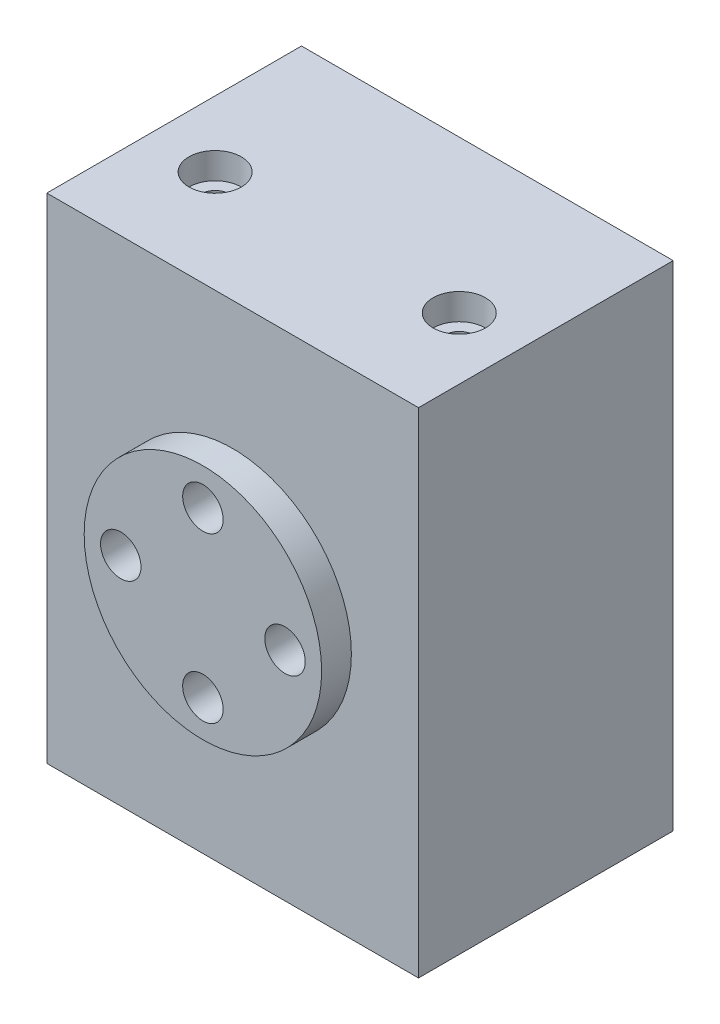
SolidWorks part; units mm, degrees
ref_plane "Front Plane" through (0, 0, 0) normal (0, 0, 1) x (1, 0, 0)
ref_plane "Top Plane" through (0, 0, 0) normal (0, 1, 0) x (1, 0, 0)
ref_plane "Right Plane" through (0, 0, 0) normal (1, 0, 0) x (0, 0, -1)
sketch "Sketch1" plane through (0, 0, 0) normal (0, 0, 1) x (1, 0, 0)
  circle A0 centre (0, 0) radius 9.975
  dimension "D1" = 19.95
extrude "Boss-Extrude1" add sketch "Sketch1" along normal blind 2.5
sketch "Sketch3" plane through (0, 0, 0) normal (0, 0, -1) x (-1, 0, 0)
  line L0 (15.615, 20.75) -> (15.615, -20.75)
  line L1 (-12.615, 17.75) -> (12.615, 17.75)
  line L2 (-12.615, 17.75) -> (-12.615, -17.75)
  line L3 (-12.615, -17.75) -> (12.615, -17.75)
  line L4 (12.615, 17.75) -> (12.615, -17.75)
  line L5 (-12.615, 17.75) -> (12.615, -17.75) construction
  line L6 (-12.615, -17.75) -> (12.615, 17.75) construction
  line L7 (-15.615, -20.75) -> (15.615, -20.75)
  line L8 (-15.615, 20.75) -> (-15.615, -20.75)
  line L9 (-15.615, 20.75) -> (15.615, 20.75)
  point P0 (0, 0)
  dimension "D1" = 35.5
  dimension "D2" = 25.23
  dimension "D3" = 3
extrude "Boss-Extrude4" add sketch "Sketch3" along normal blind 2.5 contours L2 L1 L4 L3
extrude "Boss-Extrude5" add sketch "Sketch3<5>" along normal blind 21.4
sketch "Sketch3<5>" plane through (0, 0, 0) normal (0, 0, -1) x (-1, 0, 0) same geometry as "Sketch3"
sketch "Sketch4" plane through (0, 0, -2.5) normal (0, 0, -1) x (-1, 0, 0)
  line L1 (12.615, 17.75) -> (7.415, 17.75)
  line L2 (12.615, 17.75) -> (12.615, 16.65)
  line L3 (12.615, 16.65) -> (7.415, 16.65)
  line L4 (7.415, 17.75) -> (7.415, 16.65)
  line L5 (-12.615, 17.75) -> (-7.415, 17.75)
  line L6 (-12.615, 17.75) -> (-12.615, 16.65)
  line L7 (-12.615, 16.65) -> (-7.415, 16.65)
  line L8 (-7.415, 17.75) -> (-7.415, 16.65)
  line L9 (12.615, -17.75) -> (9.415, -17.75)
  line L10 (12.615, -17.75) -> (12.615, -16.05)
  line L11 (12.615, -16.05) -> (9.415, -16.05)
  line L12 (9.415, -17.75) -> (9.415, -16.05)
  line L13 (-12.615, -17.75) -> (-9.415, -17.75)
  line L14 (-12.615, -17.75) -> (-12.615, -16.05)
  line L15 (-12.615, -16.05) -> (-9.415, -16.05)
  line L16 (-9.415, -17.75) -> (-9.415, -16.05)
  dimension "D1" = 1.1
  dimension "D2" = 5.2
  dimension "D3" = 5.2
  dimension "D4" = 1.1
  dimension "D5" = 3.2
  dimension "D6" = 1.7
  dimension "D7" = 3.2
  dimension "D8" = 1.7
extrude "Boss-Extrude6" add sketch "Sketch4" along normal blind 18.9 contours L2 L1 L4 L3 | L6 L5 L8 L7 | L10 L9 L12 L11 | L14 L13 L16 L15
sketch "Sketch6" plane through (0, 0, -2.5) normal (0, 0, -1) x (-1, 0, 0)
  line L1 (9.415, -17.75) -> (-9.415, -17.75)
  line L2 (9.415, -17.75) -> (9.415, -16.05)
  line L3 (9.415, -16.05) -> (-9.415, -16.05)
  line L4 (-9.415, -17.75) -> (-9.415, -16.05)
extrude "Boss-Extrude7" add sketch "Sketch6" along normal blind 5.3
sketch "Sketch2" plane through (0, 0, 2.5) normal (0, 0, 1) x (1, 0, 0)
  circle A0 centre (0, 0) radius 7 construction
  circle A1 centre (7, 0) radius 1.6
  circle A2 centre (0, -7) radius 1.6
  circle A3 centre (-7, 0) radius 1.6
  circle A4 centre (0, 7) radius 1.6
  point P14 (0, 0)
  dimension "D1" = 14
  dimension "D2" = 3.2
  dimension "D3" = 4
extrude "Cut-Extrude1" cut sketch "Sketch2" against normal blind 37
hole_wizard "CBORE for M3 Hex Socket Head Cap Screw1" positions "Sketch7" profile "Sketch8" counterbore size "M3" standard "ISO" end condition through all
sketch "Sketch7" plane through (0, 0, -2.5) normal (0, 0, -1) x (-1, 0, 0)
  circle A0 centre (0, 0) radius 6.9 construction
  point P0 (0, 6.9)
  point P4 (-6.9, 0)
  point P6 (6.9, 0)
  point P9 (0, -6.9)
sketch "Sketch8" plane through (0, 6.9, -2.5) normal (1, 0, 0) x (0, 1, 0)
  line L0 (0, 0) -> (0, 5)
  line L1 (0, 5) -> (1.7, 5)
  line L3 (1.7, 5) -> (1.7, 2.2)
  line L4 (1.7, 2.2) -> (3, 2.2)
  line L5 (3, 2.2) -> (3, 0)
  line L7 (3, 0) -> (0, 0)
  line L11 (0, -6.35) -> (0, 107.95) construction
  dimension "Thru Hole Dia." = 3.4
  dimension "Thru Hole Depth" = 5
  dimension "C'Bore Dia." = 6
  dimension "C'Bore Depth" = 2.2
hole_wizard "CBORE for M2 Hex Socket Head Cap Screw1" positions "Sketch9" profile "Sketch10" counterbore size "M2" standard "ISO" end condition up to next
sketch "Sketch9" plane through (0, 20.75, 0) normal (0, 1, 0) x (1, 0, 0)
  point P0 (-10.0818, 8.61)
  point P2 (10.4297, 8.61)
sketch "Sketch10" plane through (-10.0818, 20.75, -8.61) normal (1, 0, 0) x (0, 0, 1)
  line L0 (0, 0) -> (0, 4.1)
  line L1 (0, 4.1) -> (1.2, 4.1)
  line L3 (1.2, 4.1) -> (1.2, 2.2)
  line L4 (1.2, 2.2) -> (2.2, 2.2)
  line L5 (2.2, 2.2) -> (2.2, 0)
  line L7 (2.2, 0) -> (0, 0)
  line L11 (0, -6.35) -> (0, 107.95) construction
  dimension "Thru Hole Dia." = 2.4
  dimension "Thru Hole Depth" = 4.1
  dimension "C'Bore Dia." = 4.4
  dimension "C'Bore Depth" = 2.2
hole_wizard "CBORE for M2 Hex Socket Head Cap Screw2" positions "Sketch15" profile "Sketch16" counterbore size "M2" standard "ISO"
sketch "Sketch15" plane through (0, -20.75, 0) normal (0, -1, 0) x (-1, 0, 0)
  point P0 (-10.1683, 4.86)
  point P8 (10.3453, 4.86)
sketch "Sketch16" plane through (10.1683, -20.75, -4.86) normal (1, 0, 0) x (0, 0, -1)
  line L0 (0, 0) -> (0, 5.5811)
  line L1 (0, 5.5811) -> (1.3, 4.8)
  line L2 (1.3, 4.8) -> (1.3, 3.5)
  line L3 (1.3, 3.5) -> (2.2, 3.5)
  line L4 (2.2, 3.5) -> (2.2, 0)
  line L5 (2.2, 0) -> (0, 0)
  line L10 (0, 5.5811) -> (-1.3, 4.8) construction
  line L11 (0, -6.35) -> (0, 107.95) construction
  dimension "Hole Dia." = 2.6
  dimension "Hole Depth" = 4.8
  dimension "C'Bore Dia." = 4.4
  dimension "C'Bore Depth" = 3.5
  dimension "Drill Angle" = 118
